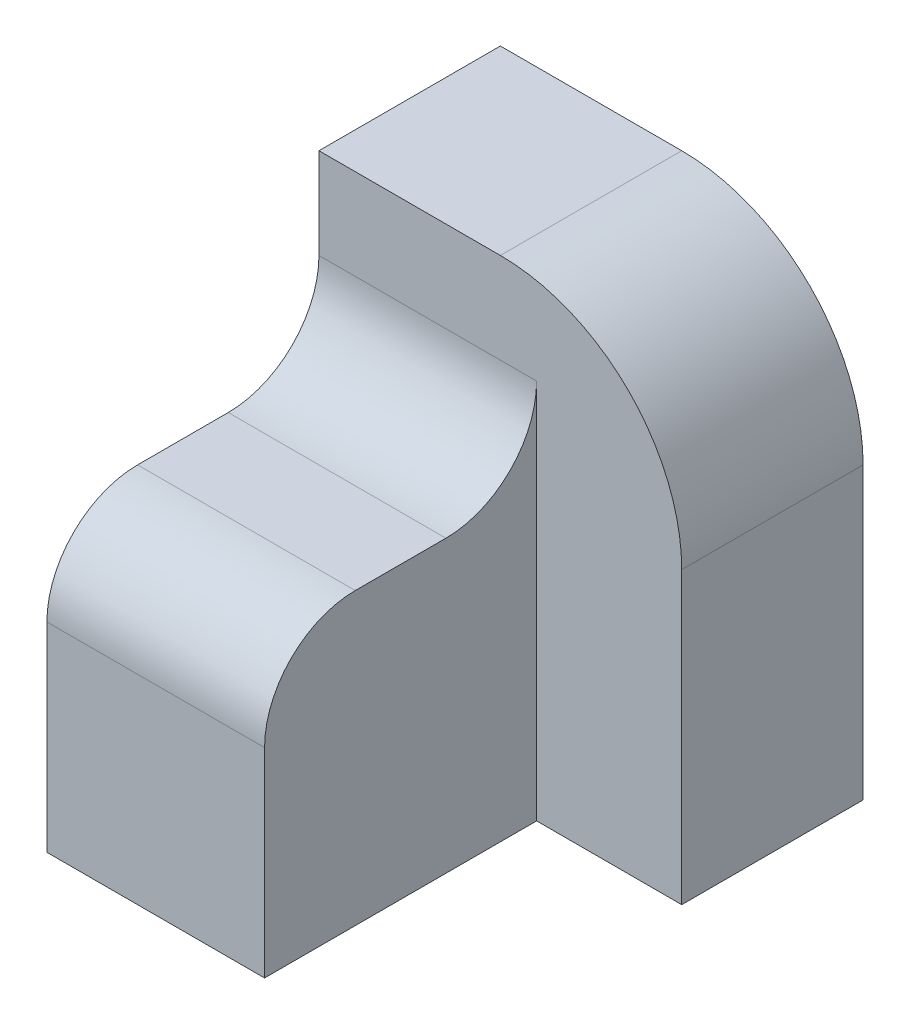
SolidWorks part; units mm, degrees
note: The reader was unsure of these and kept them because the rebuilt part matched: shared geometry of "Sketch1<5>".
ref_plane "Front Plane" through (0, 0, 0) normal (0, 0, 1) x (1, 0, 0)
ref_plane "Top Plane" through (0, 0, 0) normal (0, 1, 0) x (1, 0, 0)
ref_plane "Right Plane" through (0, 0, 0) normal (1, 0, 0) x (0, 0, -1)
sketch "Sketch1" plane through (0, 0, 0) normal (0, 1, 0) x (1, 0, 0)
  line L0 (0, 0) -> (0, 50)
  line L1 (0, 50) -> (40, 50)
  line L2 (40, 50) -> (40, 30)
  line L3 (40, 30) -> (0, 30)
  line L4 (0, 30) -> (24, 30)
  line L5 (24, 30) -> (24, 0)
  line L6 (24, 0) -> (0, 0)
  dimension "D1" = 50
  dimension "D2" = 40
  dimension "D3" = 20
  dimension "D4" = 24
sketch "Sketch2" plane through (0, 0, 0) normal (1, 0, 0) x (0, 0, -1)
  line L0 (0, 0) -> (0, 22)
  line L1 (10, 32) -> (20, 32)
  line L2 (30, 42) -> (30, 0)
  line L3 (0, 0) -> (50, 0) construction
  arc A0 (0, 22) -> (10, 32) centre (10, 22) cw
  arc A1 (20, 32) -> (30, 42) centre (20, 42) ccw
  dimension "D1" = 10
  dimension "D2" = 10
  dimension "D3" = 32
extrude "Boss-Extrude1" add sketch "Sketch1" along normal blind 60 contours L6 L5 L3 L0
extrude "Cut-Extrude1" cut sketch "Sketch2" against normal through all and the other way through all contours L0 A0 L1 A1 L2
extrude "Boss-Extrude2" add sketch "Sketch1<5>" along normal blind 52 contours L3 L2 L1 L0
sketch "Sketch1<5>" plane through (0, 0, 0) normal (0, 1, 0) x (1, 0, 0) same geometry as "Sketch1"
sketch "Sketch5" plane through (0, 0, -30) normal (0, 0, 1) x (1, 0, 0)
  line L0 (40, 52) -> (0, 52) construction
  line L1 (40, 52) -> (40, 0) construction
  arc A0 (20, 52) -> (40, 32) centre (20, 32) cw
  dimension "D1" = 20
  dimension "D2" = 20
  dimension "D3" = 20
extrude "Cut-Extrude3" cut sketch "Sketch5" against normal blind 20 and the other way through all
